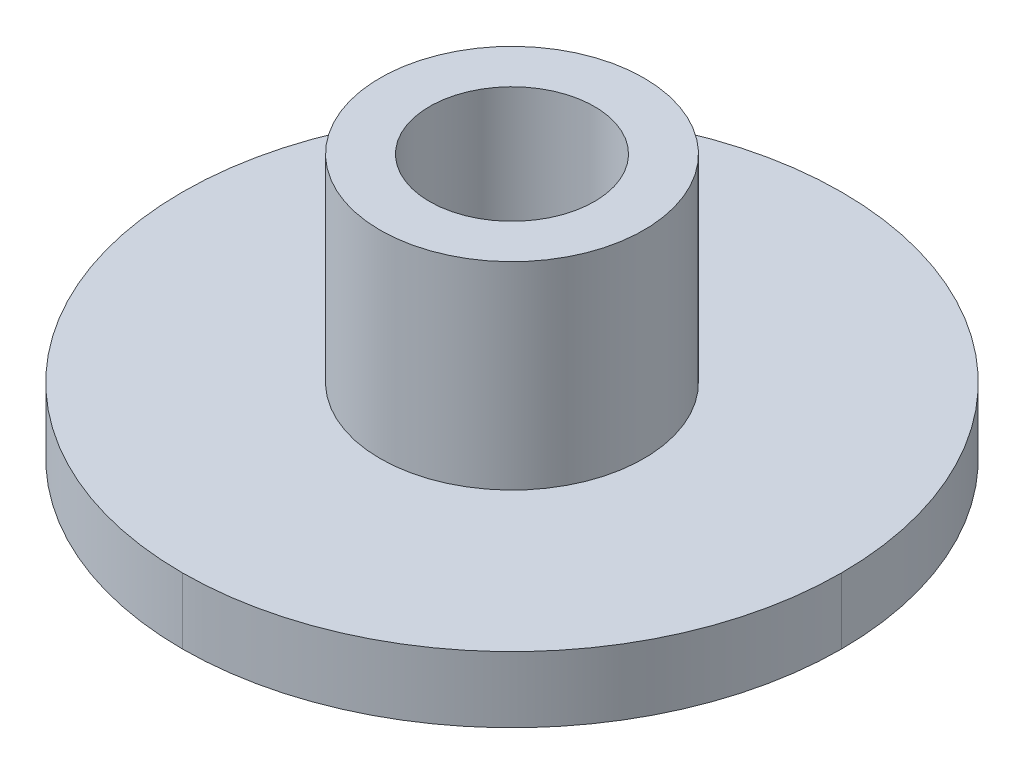
SolidWorks part; units mm, degrees
ref_plane "Спереди" through (0, 0, 0) normal (0, 0, 1) x (1, 0, 0)
ref_plane "Сверху" through (0, 0, 0) normal (0, 1, 0) x (1, 0, 0)
ref_plane "Справа" through (0, 0, 0) normal (1, 0, 0) x (0, 0, -1)
sketch "Эскиз1" plane through (0, 0, 0) normal (0, 1, 0) x (1, 0, 0)
  line L1 (0, 0) -> (40, 0)
  line L2 (0, 0) -> (0, 40)
  line L3 (0, 40) -> (40, 40)
  line L4 (40, 0) -> (40, 40)
  dimension "D1" = 40
  dimension "D2" = 40
extrude "Вытянуть1" add sketch "Эскиз1" along normal blind 4
sketch "Эскиз2" plane through (0, 4, 0) normal (0, 1, 0) x (1, 0, 0)
  line L0 (40, 40) -> (0, 40) construction
  line L1 (40, 0) -> (40, 40) construction
  circle A0 centre (20, 20) radius 8
  circle A1 centre (20, 20) radius 5
  point P2 (20, 40)
  point P3 (40, 20)
  dimension "D1" = 16
  dimension "D2" = 10
extrude "Вытянуть2" add sketch "Эскиз2" along normal blind 12
fillet "Скругление1" radius 20 4 edges at (40, 2, 0) (0, 2, 0) (0, 2, -40) (40, 2, -40)
